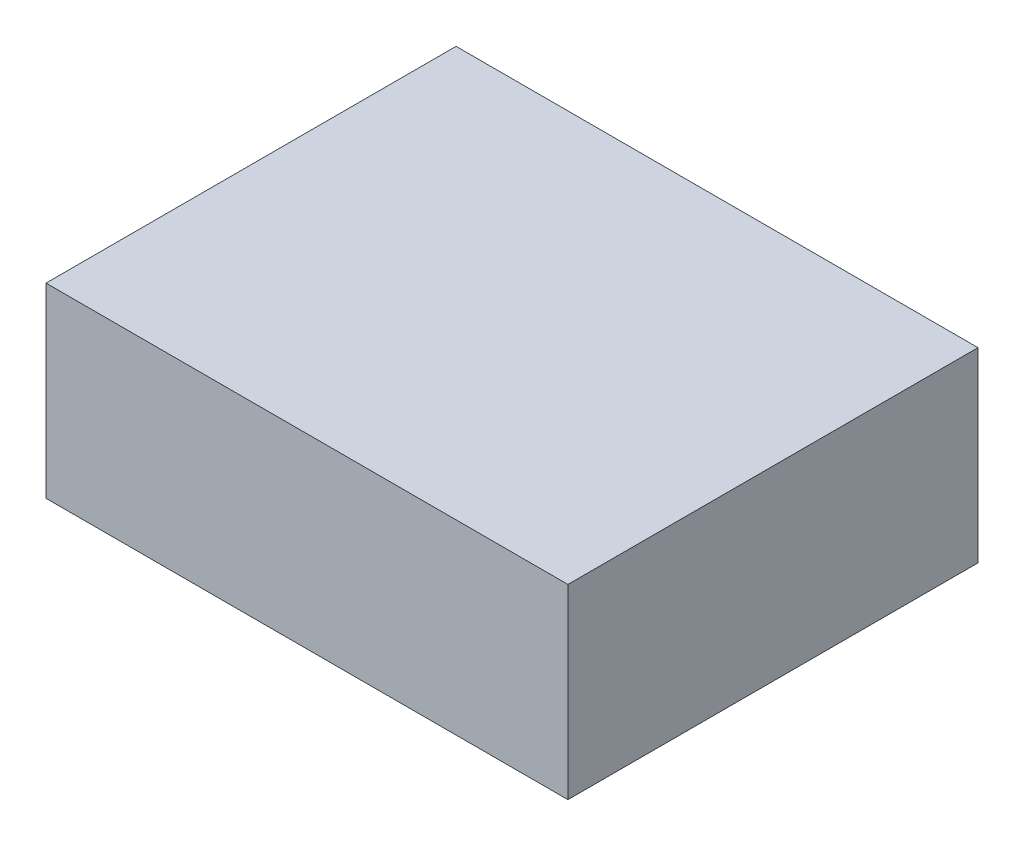
SolidWorks part; units mm, degrees
ref_plane "Front" through (0, 0, 0) normal (0, 0, 1) x (1, 0, 0)
ref_plane "Top" through (0, 0, 0) normal (0, 1, 0) x (1, 0, 0)
ref_plane "Right" through (0, 0, 0) normal (1, 0, 0) x (0, 0, -1)
sketch "Sketch1" plane through (0, 0, 0) normal (0, 1, 0) x (1, 0, 0)
  line L1 (-70, 55) -> (70, 55)
  line L2 (-70, 55) -> (-70, -55)
  line L3 (-70, -55) -> (70, -55)
  line L4 (70, 55) -> (70, -55)
  line L5 (-70, 55) -> (70, -55) construction
  line L6 (-70, -55) -> (70, 55) construction
  point P0 (0, 0)
  dimension "D1" = 140
  dimension "D2" = 110
extrude "Boss-Extrude1" add sketch "Sketch1" along normal blind 50
